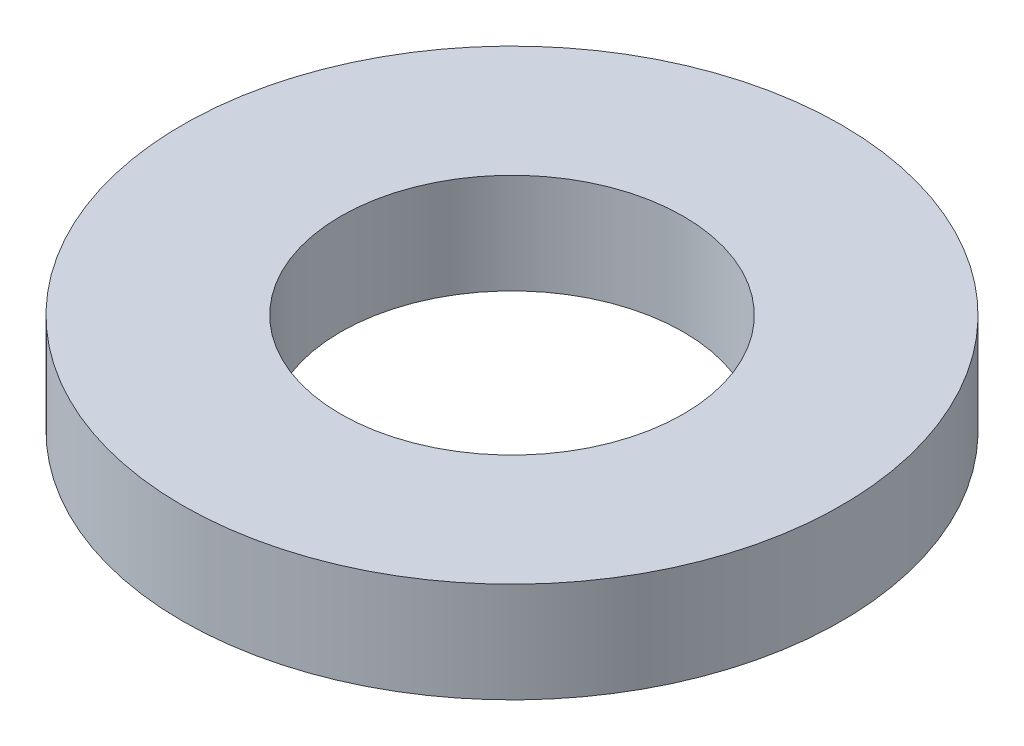
SolidWorks part; units mm, degrees
ref_plane "Front Plane" through (0, 0, 0) normal (0, 0, 1) x (1, 0, 0)
ref_plane "Top Plane" through (0, 0, 0) normal (0, 1, 0) x (1, 0, 0)
ref_plane "Right Plane" through (0, 0, 0) normal (1, 0, 0) x (0, 0, -1)
sketch "Sketch1" plane through (0, 0, 0) normal (0, 1, 0) x (1, 0, 0)
  circle A0 centre (0, 0) radius 62.5
  dimension "FLANGE_OD" = 125
extrude "Boss-Extrude1" add sketch "Sketch1" along normal blind 19
sketch "Sketch2" plane through (0, 0, 0) normal (0, 1, 0) x (1, 0, 0)
  circle A0 centre (0, 0) radius 32.5
  dimension "BORE_D" = 65
extrude "Cut-Extrude1" cut sketch "Sketch2" along normal through all
sketch "Sketch3" plane through (0, 19, 0) normal (0, 1, 0) x (1, 0, 0)
  circle A0 centre (0, 0) radius 23.3371 construction
  circle A1 centre (-23.3371, 0) radius 5.1435
  dimension "BOLT_D" = 10.2871
  dimension "BOLT_PCD" = 46.6741
extrude "Cut-Extrude2" cut sketch "Sketch3" against normal blind 15.5253 rebuild error yes
pattern_circular "CirPattern1" count 3 over 360 rebuild error yes
